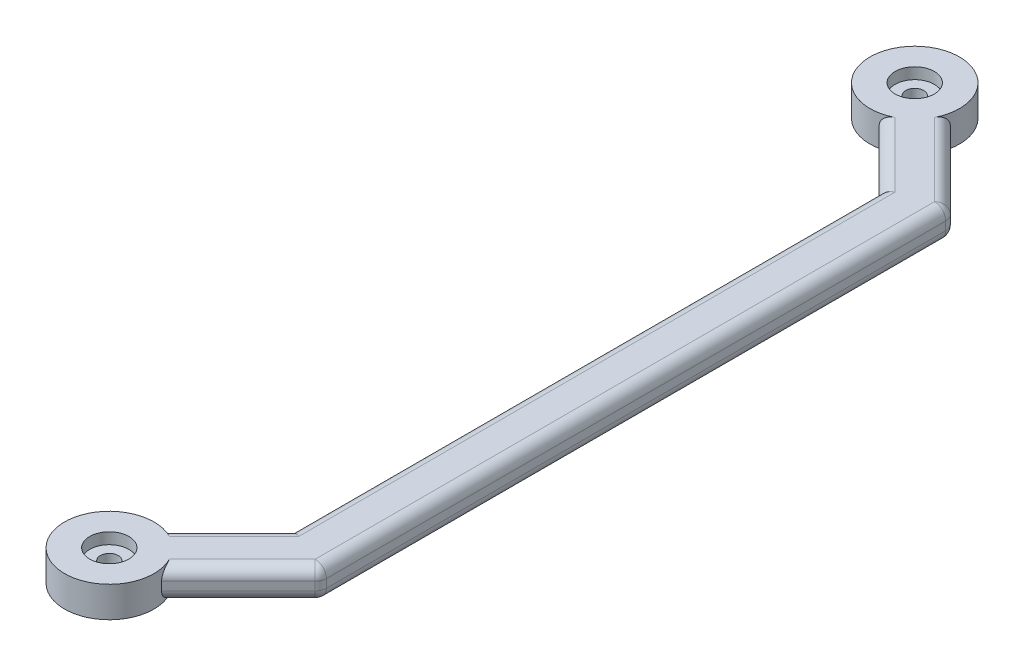
SolidWorks part; units mm, degrees
ref_plane "Ön Düzlem" through (0, 0, 0) normal (0, 0, 1) x (1, 0, 0)
ref_plane "Üst Düzlem" through (0, 0, 0) normal (0, 1, 0) x (1, 0, 0)
ref_plane "Sağ Düzlem" through (0, 0, 0) normal (1, 0, 0) x (0, 0, -1)
sketch "Sketch1" plane through (0, 0, 0) normal (0, 1, 0) x (1, 0, 0)
  line L0 (0, 72) -> (17.6777, 54.3223) construction
  line L1 (17.6777, 54.3223) -> (17.6777, 0) construction
  line L2 (1.4951, 64.1409) -> (13.1777, 52.4584)
  line L3 (13.1777, 52.4584) -> (13.1777, 0)
  line L4 (7.8591, 70.5049) -> (22.1777, 56.1863)
  line L5 (22.1777, 56.1863) -> (22.1777, 0)
  line L6 (-3.182, 68.818) -> (13.1777, 52.4584) construction
  line L7 (3.182, 75.182) -> (22.1777, 56.1863) construction
  line L8 (0, 0) -> (55.3111, 0) construction
  line L9 (17.6777, -54.3223) -> (17.6777, 0) construction
  line L10 (0, -72) -> (17.6777, -54.3223) construction
  line L11 (22.1777, -56.1863) -> (22.1777, 0)
  line L12 (7.8591, -70.5049) -> (22.1777, -56.1863)
  line L13 (13.1777, -52.4584) -> (13.1777, 0)
  line L14 (1.4951, -64.1409) -> (13.1777, -52.4584)
  arc A0 (7.8591, 70.5049) -> (1.4951, 64.1409) centre (0, 72) ccw
  circle A2 centre (0, 72) radius 1.6
  circle A3 centre (0, -72) radius 1.6
  arc A4 (7.8591, -70.5049) -> (1.4951, -64.1409) centre (0, -72) cw
  dimension "D1" = 3.2
  dimension "D2" = 16
  dimension "D3" = 72
  dimension "D4" = 25
  dimension "D5" = 4.5
  dimension "D6" = 4.5
extrude "Boss-Extrude1" add sketch "Sketch1" along normal blind 5.5
sketch "Sketch2" plane through (0, 0, 0) normal (0, -1, 0) x (1, 0, 0)
  circle A0 centre (0, -72) radius 1.6 construction
  circle A1 centre (0, -72) radius 1.6
  circle A2 centre (0, -72) radius 3.5
  dimension "D1" = 7
fillet "Fillet1" radius 2 2 edges at (13.1777, 5.5, 0) (22.1777, 0, 0)
fillet "Fillet2" radius 2 2 edges at (22.1777, 5.5, 0) (13.1777, 0, 0)
fillet "Fillet3" radius 2 7 edges at (14.0184, 0, -64.3456) (21.5919, 0.5858, -56.7721) (22.1777, 2.75, -56.1863) (21.5919, 4.9142, -56.7721) (8.3364, 5.5, -57.2997) (8.3364, 0, -57.2997) (14.0184, 5.5, -64.3456)
fillet "Fillet4" radius 2 7 edges at (14.0184, 0, 64.3456) (21.5919, 0.5858, 56.7721) (22.1777, 2.75, 56.1863) (21.5919, 4.9142, 56.7721) (8.3364, 5.5, 57.2997) (14.0184, 5.5, 64.3456) (8.3364, 0, 57.2997)
sketch "Sketch3" plane through (0, 5.5, 0) normal (0, 1, 0) x (1, 0, 0)
  circle A0 centre (0, 72) radius 1.6 construction
  circle A1 centre (0, 72) radius 1.6
  circle A2 centre (0, 72) radius 3.5
extrude "Cut-Extrude2" cut sketch "Sketch3" against normal blind 2
sketch "Sketch6" plane through (0, 5.5, 0) normal (0, 1, 0) x (1, 0, 0)
  circle A0 centre (0, -72) radius 1.6 construction
  circle A1 centre (0, -72) radius 1.6
  circle A2 centre (0, -72) radius 3.5
extrude "Cut-Extrude3" cut sketch "Sketch6" against normal blind 2
